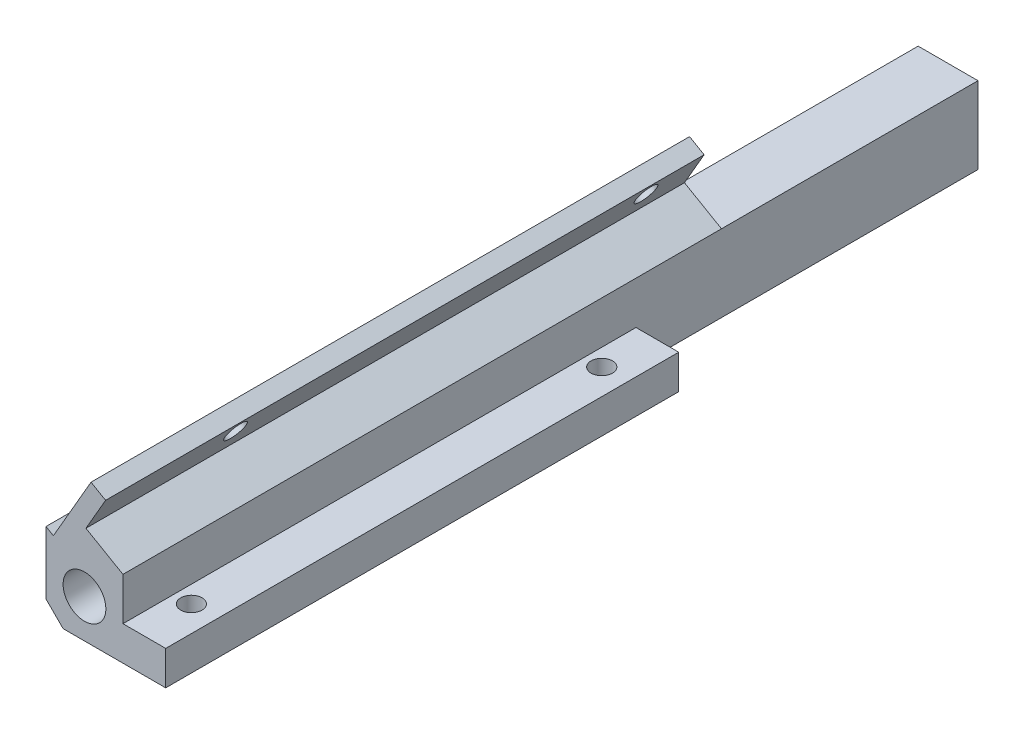
SolidWorks part; units mm, degrees
ref_plane "Front Plane" through (0, 0, 0) normal (0, 0, 1) x (1, 0, 0)
ref_plane "Top Plane" through (0, 0, 0) normal (0, 1, 0) x (1, 0, 0)
ref_plane "Right Plane" through (0, 0, 0) normal (1, 0, 0) x (0, 0, -1)
sketch "Sketch1" plane through (0, 0, 0) normal (0, 1, 0) x (1, 0, 0)
  line L1 (0, 0) -> (77.47, 0)
  line L2 (0, 0) -> (0, 127)
  line L3 (0, 127) -> (77.47, 127)
  line L4 (77.47, 0) -> (77.47, 127)
  dimension "D1" = 77.47
  dimension "D2" = 127
extrude "Boss-Extrude1" add sketch "Sketch1" along normal blind 11.43
sketch "Sketch2" plane through (0, 0, 0) normal (0, 0, 1) x (1, 0, 0)
  line L0 (5.715, 5.715) -> (71.755, 5.715) construction
  line L1 (38.735, 11.43) -> (38.735, 0) construction
  line L2 (0, 11.43) -> (77.47, 11.43) construction
  line L3 (0, 0) -> (77.47, 0) construction
  circle A0 centre (5.715, 5.715) radius 3.175
  circle A1 centre (71.755, 5.715) radius 3.175
  point P10 (38.735, 5.715)
  dimension "D1" = 6.35
  dimension "D2" = 66.04
extrude "Cut-Extrude1" cut sketch "Sketch2" against normal through all
sketch "Sketch3" plane through (0, 11.43, 0) normal (0, 1, 0) x (1, 0, 0)
  line L0 (11.43, 127) -> (11.43, 88.9)
  line L1 (77.47, 127) -> (0, 127) construction
  line L2 (11.43, 127) -> (66.04, 127)
  line L3 (66.04, 127) -> (66.04, 88.9)
  line L4 (53.34, 76.2) -> (24.13, 76.2)
  line L5 (0, 127) -> (0, 0) construction
  arc A0 (66.04, 88.9) -> (53.34, 76.2) centre (53.34, 88.9) cw
  arc A1 (24.13, 76.2) -> (11.43, 88.9) centre (24.13, 88.9) cw
  point P10 (38.735, 127)
  dimension "D1" = 12.7
  dimension "D2" = 11.43
  dimension "D3" = 50.8
extrude "Cut-Extrude2" cut sketch "Sketch3" against normal through all
sketch "Sketch4" plane through (0, 0, -127) normal (0, 0, -1) x (-1, 0, 0)
  line L0 (-11.43, 0) -> (-11.43, 11.43) construction
  line L1 (-66.04, 11.43) -> (-11.43, 11.43)
  line L2 (-66.04, 11.43) -> (-66.04, 5.08)
  line L3 (-66.04, 5.08) -> (-11.43, 5.08)
  line L4 (-11.43, 11.43) -> (-11.43, 5.08)
  line L5 (-11.43, 0) -> (0, 0) construction
  dimension "D1" = 5.08
extrude "Cut-Extrude3" cut sketch "Sketch4" against normal through all
chamfer "Chamfer1" distance 2.54 angle 45 4 edges at (0, 0, -63.5) (0, 11.43, -63.5) (77.47, 0, -63.5) (77.47, 11.43, -63.5)
sketch "Sketch5" plane through (0, 11.43, 0) normal (0, 1, 0) x (1, 0, 0)
  line L0 (11.43, 88.9) -> (11.43, 76.2)
  line L1 (11.43, 0) -> (11.43, 88.9) construction
  line L2 (11.43, 76.2) -> (77.47, 76.2)
  line L3 (77.47, 127) -> (77.47, 0) construction
  line L4 (77.47, 76.2) -> (77.47, 127)
  line L8 (24.13, 76.2) -> (53.34, 76.2) construction
  line L9 (77.47, 127) -> (11.43, 127)
  line L10 (11.43, 127) -> (11.43, 88.9)
extrude "Cut-Extrude4" cut sketch "Sketch5" against normal through all
sketch "Sketch6" plane through (0, 11.43, 0) normal (0, 1, 0) x (1, 0, 0)
  line L0 (24.13, 76.2) -> (24.13, 0)
  line L1 (11.43, 76.2) -> (66.04, 76.2) construction
  line L2 (66.04, 0) -> (11.43, 0) construction
  line L3 (24.13, 0) -> (77.47, 0)
  line L4 (77.47, 0) -> (77.47, 76.2)
  line L5 (77.47, 76.2) -> (24.13, 76.2)
  line L6 (11.43, 0) -> (11.43, 76.2) construction
  dimension "D1" = 12.7
extrude "Cut-Extrude5" cut sketch "Sketch6" against normal through all
sketch "Sketch7" plane through (0, 5.08, 0) normal (0, 1, 0) x (1, 0, 0)
  line L0 (11.43, 76.2) -> (24.13, 76.2) construction
  line L1 (11.43, 0) -> (11.43, 76.2) construction
  circle A0 centre (13.97, 68.58) radius 1.5875
  circle A1 centre (13.97, 7.62) radius 1.5875
  point P2 (0, 0)
  dimension "D1" = 3.175
  dimension "D2" = 7.62
  dimension "D3" = 68.58
  dimension "D4" = 2.54
extrude "Cut-Extrude6" cut sketch "Sketch7" against normal through all
sketch "Sketch17" plane through (0, 0, 0) normal (0, 0, 1) x (1, 0, 0)
  line L0 (0, 8.89) -> (0, 11.8699)
  line L1 (0, 11.8699) -> (5.588, 21.5486)
  line L2 (5.588, 21.5486) -> (8.8517, 19.6643)
  line L3 (8.8517, 19.6643) -> (5.9307, 14.605)
  line L4 (5.9307, 14.605) -> (11.43, 11.43)
  line L5 (0, 8.89) -> (0, 2.54) construction
  line L6 (11.43, 11.43) -> (2.54, 11.43)
  line L7 (2.54, 11.43) -> (0, 8.89)
  dimension "D1" = 11.176
  dimension "D2" = 5.842
  dimension "D3" = 6.35
  dimension "D4" = 60
extrude "Boss-Extrude5" add sketch "Sketch17" against normal blind 88.9
sketch "Sketch18" plane through (0, 0, 0) normal (0, 0, 1) x (1, 0, 0)
  line L0 (2.54, 0) -> (17.78, 0) construction
  line L1 (2.54, 0) -> (24.13, 0) construction
  line L2 (11.43, 5.08) -> (11.43, 11.43) construction
  line L3 (17.78, 0) -> (24.13, 0)
  line L4 (24.13, 0) -> (24.13, 5.08)
  line L5 (24.13, 5.08) -> (17.78, 5.08)
  line L6 (24.13, 5.08) -> (11.43, 5.08) construction
  line L7 (17.78, 5.08) -> (17.78, 0)
  dimension "D1" = 6.35
extrude "Cut-Extrude13" cut sketch "Sketch18" against normal blind 76.2
sketch "Sketch19" plane through (-1.8761, 1.0832, 0) normal (0.866, -0.5, 0) x (0, 0, -1)
  line L1 (88.9, 15.6137) -> (0, 15.6137) construction
  line L2 (88.9, 15.6137) -> (88.9, 21.4557) construction
  circle A0 centre (20.32, 19.4237) radius 1.5875
  circle A1 centre (81.28, 19.4237) radius 1.5875
  point P4 (0, 0)
  point P5 (0, 0)
  dimension "D1" = 3.175
  dimension "D2" = 7.62
  dimension "D3" = 68.58
  dimension "D4" = 3.81
extrude "Cut-Extrude15" cut sketch "Sketch19" against normal up to next
sketch "Sketch20" plane through (-5.1398, 2.9675, 0) normal (-0.866, 0.5, 0) x (0, 0, 1)
  line L1 (-88.9, 21.4557) -> (0, 21.4557)
  line L2 (-88.9, 21.4557) -> (-88.9, 10.2797)
  line L3 (-88.9, 10.2797) -> (0, 10.2797)
  line L4 (0, 21.4557) -> (0, 10.2797)
extrude "Cut-Extrude16" cut sketch "Sketch20" against normal blind 1.27
